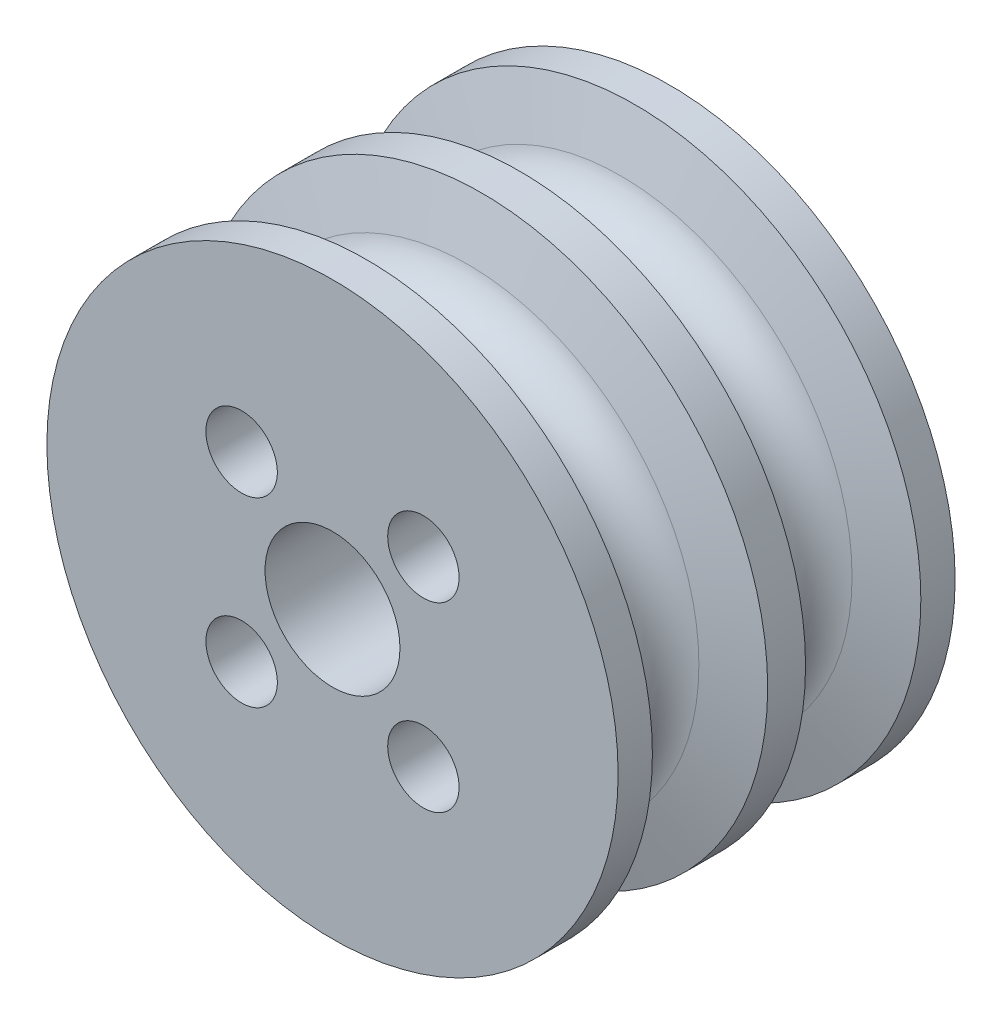
SolidWorks part; units mm, degrees
ref_plane "Front" through (0, 0, 0) normal (0, 0, 1) x (1, 0, 0)
ref_plane "Top" through (0, 0, 0) normal (0, 1, 0) x (1, 0, 0)
ref_plane "Right" through (0, 0, 0) normal (1, 0, 0) x (0, 0, -1)
ref_axis "side-side" through (80.9, 0, 0) along (-1, 0, 0)
ref_axis "up-down" through (0, 50, 0) along (0, -1, 0)
ref_axis "front-back" through (0, 0, -80.9) along (0, 0, 1)
sketch "Sketch1" plane through (0, 0, 0) normal (1, 0, 0) x (0, 0, -1)
  line L0 (-1.4883, 10.2876) -> (-0.8419, 12.7)
  line L1 (-0.8419, 12.7) -> (0.8419, 12.7)
  line L2 (0.8419, 12.7) -> (1.4883, 10.2876)
  line L3 (-5.3218, 10.2876) -> (-5.9682, 12.7)
  line L4 (-5.9682, 12.7) -> (-7.4922, 12.7)
  line L5 (5.9682, 12.7) -> (7.4922, 12.7)
  line L6 (5.3218, 10.2876) -> (5.9682, 12.7)
  line L7 (3.405, 10.8011) -> (7.1412, 10.8011) construction
  line L8 (0, 0) -> (18.8173, 0) construction
  line L9 (7.4922, 12.7) -> (7.4922, 4.127)
  line L11 (4.4922, 4.127) -> (7.4922, 4.127)
  line L13 (-7.4922, 3) -> (4.4922, 3)
  line L14 (4.4922, 4.127) -> (4.4922, 3)
  line L16 (-7.4922, 12.7) -> (-7.4922, 3)
  line L17 (0, 50) -> (0, -50) construction
  arc A0 (-5.3218, 10.2876) -> (-1.4883, 10.2876) centre (-3.405, 10.8011) ccw
  arc A1 (1.4883, 10.2876) -> (5.3218, 10.2876) centre (3.405, 10.8011) ccw
  point P2 (0, 0)
  point P19 (0, 0)
  dimension "D1" = 3.9688
  dimension "D9" = 3.405
  dimension "D10" = 21.6023
  dimension "D11" = 6.8101
  dimension "D2" = 30
  dimension "D3" = 25.4
  dimension "D4" = 8.254
  dimension "D5" = 6
  dimension "D6" = 3
  dimension "D7" = 1.524
  dimension "D8" = 1.524
revolve "Revolve1" add sketch "Sketch1" angle 360 about L8
sketch "Sketch2" plane through (0, 0, -7.4922) normal (0, 0, -1) x (-1, 0, 0)
  line L1 (-4.0411, 4.0411) -> (4.0411, 4.0411) construction
  line L2 (-4.0411, 4.0411) -> (-4.0411, -4.0411) construction
  line L3 (-4.0411, -4.0411) -> (4.0411, -4.0411) construction
  line L4 (4.0411, 4.0411) -> (4.0411, -4.0411) construction
  circle A0 centre (0, 0) radius 5.715 construction
  circle A1 centre (4.0411, 4.0411) radius 1.5875
  circle A2 centre (-4.0411, 4.0411) radius 1.5875
  circle A3 centre (-4.0411, -4.0411) radius 1.5875
  circle A4 centre (4.0411, -4.0411) radius 1.5875
  point P15 (0, 0)
  point P16 (0, 0)
  point P17 (0, 0)
  point P18 (0, 0)
  point P19 (0, 0)
  dimension "D1" = 11.43
  dimension "D2" = 3.175
extrude "Cut-Extrude1" cut sketch "Sketch2" against normal up to surface (14.9844 mm away) up to face at (3, 0, 7.4922)
